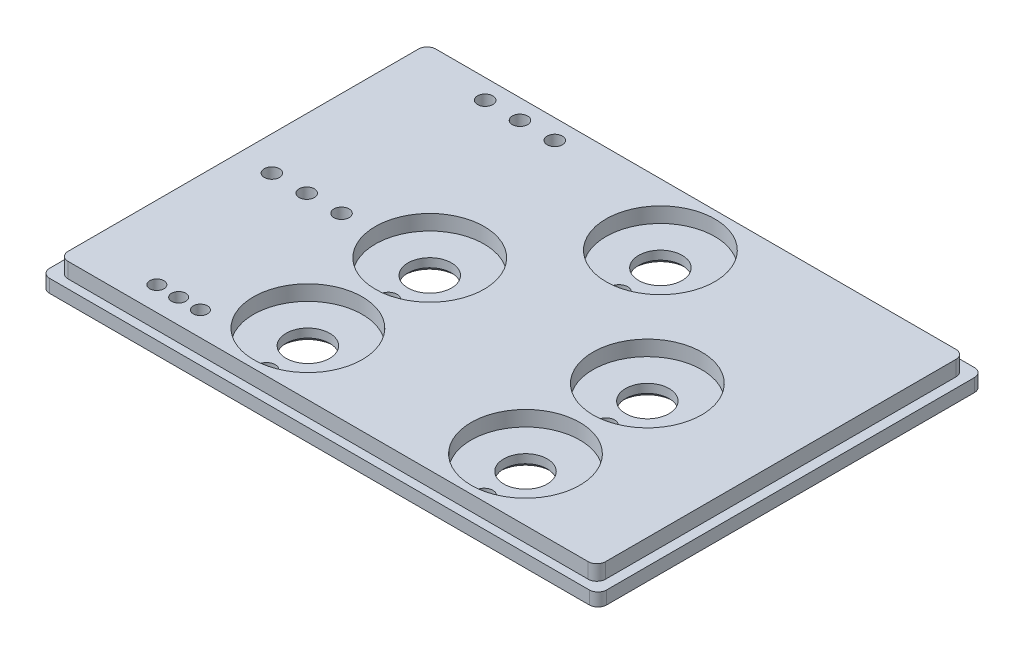
SolidWorks part; units mm, degrees
ref_plane "Спереди" through (0, 0, 0) normal (0, 0, 1) x (1, 0, 0)
ref_plane "Сверху" through (0, 0, 0) normal (0, 1, 0) x (1, 0, 0)
ref_plane "Справа" through (0, 0, 0) normal (1, 0, 0) x (0, 0, -1)
sketch "Эскиз1" plane through (0, 37.5, 0) normal (0, 1, 0) x (1, 0, 0)
  line L1 (127, -2) -> (127, 87) construction
  line L2 (-2, 87) -> (0, 87) construction
  line L3 (127, -2) -> (127, 87) construction
  line L4 (127, -2) -> (0, -2) construction
  line L5 (127, -2) -> (-2, -2) construction
  line L6 (-2, 87) -> (-2, -2) construction
  line L7 (-2, 87) -> (-2, -2) construction
  line L8 (62.5, 87) -> (62.5, -2) construction
  line L9 (-2, 87) -> (0, 87) construction
  line L10 (-2, 86.75) -> (127, 86.75)
  line L11 (-2, 86.75) -> (-2, -1.75)
  line L12 (-2, -1.75) -> (127, -1.75)
  line L13 (127, 86.75) -> (127, -1.75)
  line L14 (-2, 86.75) -> (127, -1.75) construction
  line L15 (-2, -1.75) -> (127, 86.75) construction
  point P8 (62.5, 42.5)
  dimension "D1" = 0.25
  dimension "D2" = 0.25
extrude "Бобышка-Вытянуть1" add sketch "Эскиз1" along normal blind 3
sketch "Эскиз2" plane through (0, 40.5, 0) normal (0, 1, 0) x (1, 0, 0)
  circle A0 centre (43.6, 14.5) radius 5 construction
  circle A1 centre (43.6, 14.5) radius 5 construction
  circle A3 centre (43.6, 42.5) radius 5 construction
  circle A4 centre (68.6, 70.5) radius 5 construction
  circle A5 centre (68.6, 70.5) radius 5 construction
  circle A6 centre (43.6, 42.5) radius 5 construction
  circle A7 centre (93.6, 42.5) radius 5 construction
  circle A8 centre (93.6, 42.5) radius 5 construction
  circle A9 centre (93.6, 14.5) radius 5 construction
  circle A10 centre (93.6, 14.5) radius 5 construction
  circle A11 centre (43.6, 14.5) radius 5
  circle A12 centre (43.6, 42.5) radius 5
  circle A13 centre (68.6, 70.5) radius 5
  circle A14 centre (93.6, 42.5) radius 5
  circle A15 centre (93.6, 14.5) radius 5
  dimension "D1" = 0
extrude "Вырез-Вытянуть1" cut sketch "Эскиз2" against normal through all
sketch "Эскиз3" plane through (0, 40.5, 0) normal (0, 1, 0) x (1, 0, 0)
  circle A0 centre (34.5998, 80.2301) radius 1.75
  circle A1 centre (27.5999, 5.8) radius 1.5
  circle A2 centre (27.5999, 5.8) radius 1.5 construction
  circle A3 centre (22.5999, 5.8) radius 1.5
  circle A4 centre (22.5999, 5.8) radius 1.5 construction
  circle A5 centre (17.5999, 5.8) radius 1.5
  circle A6 centre (17.5999, 5.8) radius 1.5 construction
  circle A7 centre (34.5998, 80.2301) radius 1.5
  circle A8 centre (34.5998, 80.2301) radius 1.5 construction
  circle A9 centre (26.6, 80.2299) radius 1.5
  circle A10 centre (26.6, 80.2299) radius 1.5 construction
  circle A11 centre (18.5998, 80.2301) radius 1.5
  circle A12 centre (18.5998, 80.2301) radius 1.5 construction
  circle A13 centre (8.5998, 41.2301) radius 1.5
  circle A14 centre (8.5998, 41.2301) radius 1.5 construction
  circle A15 centre (16.5998, 41.2301) radius 1.5
  circle A16 centre (16.5998, 41.2301) radius 1.5 construction
  circle A17 centre (24.6, 41.2299) radius 1.5
  circle A18 centre (24.6, 41.2299) radius 1.5 construction
  circle A19 centre (26.6, 80.2299) radius 1.75
  circle A20 centre (18.5998, 80.2301) radius 1.75
  circle A21 centre (8.5998, 41.2301) radius 1.75
  circle A22 centre (16.5998, 41.2301) radius 1.75
  circle A23 centre (24.6, 41.2299) radius 1.75
  circle A24 centre (27.5999, 5.8) radius 1.625
  circle A25 centre (22.5999, 5.8) radius 1.625
  circle A26 centre (17.5999, 5.8) radius 1.625
  dimension "D10" = 3.5
  dimension "D11" = 3.25
  dimension "D1" = 0
  dimension "D2" = 0
  dimension "D3" = 0
  dimension "D4" = 0
  dimension "D5" = 0
  dimension "D6" = 0
  dimension "D7" = 0
  dimension "D8" = 0
  dimension "D9" = 0
extrude "Вырез-Вытянуть2" cut sketch "Эскиз3" against normal through all
chamfer "Фаска1" distance 1 angle 45 5 edges at (93.6, 37.5, -9.5) (93.6, 37.5, -37.5) (68.6, 37.5, -65.5) (43.6, 37.5, -37.5) (43.6, 37.5, -9.5)
sketch "Эскиз6" plane through (0, 40.5, 0) normal (0, 1, 0) x (1, 0, 0)
  line L0 (125, 0) -> (0, 0) construction
  line L1 (125, 0) -> (125, 85) construction
  line L2 (125, 0) -> (0, 0) construction
  line L3 (125, 0) -> (125, 85) construction
  line L4 (0, -4) -> (0, 89) construction
  line L5 (0, -4) -> (0, 89) construction
  line L6 (125, 85) -> (0, 85) construction
  line L7 (125, 85) -> (0, 85) construction
  line L8 (62.5, 85) -> (62.5, 0) construction
  line L10 (124.75, 0.25) -> (0.25, 0.25)
  line L11 (124.75, 0.25) -> (124.75, 84.75)
  line L12 (124.75, 84.75) -> (0.25, 84.75)
  line L13 (0.25, 0.25) -> (0.25, 84.75)
  line L14 (124.75, 0.25) -> (0.25, 84.75) construction
  line L15 (124.75, 84.75) -> (0.25, 0.25) construction
  point P8 (62.5, 42.5)
  dimension "D1" = 0.25
  dimension "D2" = 0.25
extrude "Бобышка-Вытянуть3" add sketch "Эскиз6" along normal blind 3.5
sketch "Эскиз7" plane through (0, 40.5, 0) normal (0, -1, 0) x (1, 0, 0)
  circle A0 centre (26.6, -80.2299) radius 1.75 construction
  circle A1 centre (43.6, -42.5) radius 5
  circle A2 centre (43.6, -42.5) radius 5
  circle A3 centre (43.6, -14.5) radius 5
  circle A4 centre (43.6, -14.5) radius 5
  circle A5 centre (93.6, -14.5) radius 5
  circle A6 centre (93.6, -14.5) radius 5
  circle A7 centre (93.6, -42.5) radius 5
  circle A8 centre (93.6, -42.5) radius 5
  circle A9 centre (68.6, -70.5) radius 5
  circle A10 centre (68.6, -70.5) radius 5
  circle A11 centre (24.6, -41.2299) radius 1.75
  circle A12 centre (24.6, -41.2299) radius 1.75
  circle A13 centre (16.5998, -41.2301) radius 1.75
  circle A14 centre (16.5998, -41.2301) radius 1.75
  circle A15 centre (8.5998, -41.2301) radius 1.75
  circle A16 centre (8.5998, -41.2301) radius 1.75
  circle A17 centre (18.5998, -80.2301) radius 1.75
  circle A18 centre (18.5998, -80.2301) radius 1.75
  circle A19 centre (26.6, -80.2299) radius 1.75
  circle A21 centre (34.5998, -80.2301) radius 1.75
  circle A22 centre (34.5998, -80.2301) radius 1.75
  circle A25 centre (22.5999, -5.8) radius 1.625 construction
  circle A26 centre (22.5999, -5.8) radius 1.625
  circle A27 centre (17.5999, -5.8) radius 1.625 construction
  circle A28 centre (27.5999, -5.8) radius 1.625 construction
  circle A29 centre (27.5999, -5.8) radius 1.625
  circle A30 centre (17.5999, -5.8) radius 1.625
  dimension "D1" = 0
  dimension "D2" = 0
  dimension "D3" = 0
  dimension "D4" = 0
  dimension "D5" = 0
  dimension "D6" = 0
  dimension "D7" = 0
  dimension "D8" = 0
  dimension "D9" = 0
  dimension "D10" = 0
extrude "Вырез-Вытянуть3" cut sketch "Эскиз7" against normal through all
sketch "Эскиз9" plane through (0, 44, 0) normal (0, 1, 0) x (1, 0, 0)
  circle A0 centre (43.6, 14.5) radius 12.5
  circle A1 centre (43.6, 42.5) radius 12.5
  circle A2 centre (68.6, 70.5) radius 12.5
  circle A3 centre (93.6, 42.5) radius 12.5
  circle A4 centre (93.6, 14.5) radius 12.5
  dimension "D1" = 25
extrude "Вырез-Вытянуть4" cut sketch "Эскиз9" against normal blind 3.5
sketch "Эскиз10" plane through (0, 44, 0) normal (0, 1, 0) x (1, 0, 0)
  circle A0 centre (93.6, 33) radius 1.5 construction
  circle A1 centre (93.6, 33) radius 1.5 construction
  circle A2 centre (93.6, 5) radius 1.5 construction
  circle A3 centre (93.6, 5) radius 1.5 construction
  circle A4 centre (43.6, 5) radius 1.5 construction
  circle A5 centre (43.6, 5) radius 1.5 construction
  circle A6 centre (43.6, 33) radius 1.5 construction
  circle A7 centre (43.6, 33) radius 1.5 construction
  circle A8 centre (68.6, 61.0001) radius 1.5 construction
  circle A9 centre (68.6, 61.0001) radius 1.5 construction
  circle A10 centre (43.6, 5) radius 2
  circle A11 centre (43.6, 33) radius 2
  circle A12 centre (68.6, 61.0001) radius 2
  circle A13 centre (93.6, 33) radius 2
  circle A14 centre (93.6, 5) radius 2
  dimension "D1" = 0.5
sketch "Эскиз11" plane through (0, 37.5, 0) normal (0, -1, 0) x (1, 0, 0)
  circle A0 centre (43.6, -5) radius 2 construction
  circle A1 centre (43.6, -33) radius 2 construction
  circle A2 centre (93.6, -5) radius 2 construction
  circle A3 centre (93.6, -33) radius 2 construction
  circle A4 centre (68.6, -61.0001) radius 2 construction
  circle A5 centre (43.6, -5) radius 2
  circle A6 centre (43.6, -33) radius 2
  circle A7 centre (93.6, -5) radius 2
  circle A8 centre (93.6, -33) radius 2
  circle A9 centre (68.6, -61.0001) radius 2
extrude "Вырез-Вытянуть5" cut sketch "Эскиз11" against normal up to surface (3 mm away) up to face at (93.6, 40.5, -2)
sketch "Sketch1" plane through (-2, 0, 0) normal (-1, 0, 0) x (0, 0, 1)
  line L4 (-86.75, 37.5) -> (1.75, 37.5)
  line L5 (1.75, 37.5) -> (1.75, 40.5)
  line L6 (1.75, 40.5) -> (-86.75, 40.5)
  line L7 (-86.75, 40.5) -> (-86.75, 37.5)
  line L8 (-86.75, 37.5) -> (1.75, 37.5)
  line L9 (1.75, 37.5) -> (1.75, 40.5)
  line L10 (1.75, 40.5) -> (-86.75, 40.5)
  line L11 (-86.75, 40.5) -> (-86.75, 37.5)
  dimension "D1" = 0
extrude "Cut-Extrude1" cut sketch "Sketch1" against normal blind 0.5
sketch "Sketch2" plane through (127, 0, 0) normal (1, 0, 0) x (0, 0, -1)
  line L4 (-1.75, 37.5) -> (86.75, 37.5)
  line L5 (86.75, 37.5) -> (86.75, 40.5)
  line L6 (86.75, 40.5) -> (-1.75, 40.5)
  line L7 (-1.75, 40.5) -> (-1.75, 37.5)
  line L8 (-1.75, 37.5) -> (86.75, 37.5)
  line L9 (86.75, 37.5) -> (86.75, 40.5)
  line L10 (86.75, 40.5) -> (-1.75, 40.5)
  line L11 (-1.75, 40.5) -> (-1.75, 37.5)
  dimension "D1" = 0
extrude "Cut-Extrude2" cut sketch "Sketch2" against normal blind 0.5
sketch "Sketch3" plane through (124.75, 0, 0) normal (1, 0, 0) x (0, 0, -1)
  line L4 (0.25, 40.5) -> (84.75, 40.5)
  line L5 (84.75, 40.5) -> (84.75, 44)
  line L6 (84.75, 44) -> (0.25, 44)
  line L7 (0.25, 44) -> (0.25, 40.5)
  line L8 (0.25, 40.5) -> (84.75, 40.5)
  line L9 (84.75, 40.5) -> (84.75, 44)
  line L10 (84.75, 44) -> (0.25, 44)
  line L11 (0.25, 44) -> (0.25, 40.5)
  dimension "D1" = 0
extrude "Cut-Extrude3" cut sketch "Sketch3" against normal blind 0.5
sketch "Sketch4" plane through (0.25, 0, 0) normal (-1, 0, 0) x (0, 0, 1)
  line L4 (-84.75, 40.5) -> (-0.25, 40.5)
  line L5 (-0.25, 40.5) -> (-0.25, 44)
  line L6 (-0.25, 44) -> (-84.75, 44)
  line L7 (-84.75, 44) -> (-84.75, 40.5)
  line L8 (-84.75, 40.5) -> (-0.25, 40.5)
  line L9 (-0.25, 40.5) -> (-0.25, 44)
  line L10 (-0.25, 44) -> (-84.75, 44)
  line L11 (-84.75, 44) -> (-84.75, 40.5)
  dimension "D1" = 0
extrude "Cut-Extrude4" cut sketch "Sketch4" against normal blind 0.5
fillet "Fillet1" radius 2 8 edges at (126.5, 39, -86.75) (124.25, 42.25, -84.75) (126.5, 39, 1.75) (124.25, 42.25, -0.25) (0.75, 42.25, -0.25) (-1.5, 39, 1.75) (0.75, 42.25, -84.75) (-1.5, 39, -86.75)
sketch "Sketch5" plane through (0, 37.5, 0) normal (0, -1, 0) x (1, 0, 0)
  circle A0 centre (8.5998, -41.2301) radius 1.75 construction
  circle A1 centre (16.5998, -41.2301) radius 1.75 construction
  circle A2 centre (24.6, -41.2299) radius 1.75 construction
  circle A3 centre (18.5998, -80.2301) radius 1.75 construction
  circle A4 centre (26.6, -80.2299) radius 1.75 construction
  circle A5 centre (34.5998, -80.2301) radius 1.75 construction
  circle A6 centre (8.5998, -41.2301) radius 1.75 construction
  circle A7 centre (16.5998, -41.2301) radius 1.75 construction
  circle A8 centre (24.6, -41.2299) radius 1.75 construction
  circle A9 centre (18.5998, -80.2301) radius 1.75 construction
  circle A10 centre (26.6, -80.2299) radius 1.75 construction
  circle A11 centre (34.5998, -80.2301) radius 1.75 construction
  circle A12 centre (8.5998, -41.2301) radius 2.5
  circle A13 centre (16.5998, -41.2301) radius 2.5
  circle A14 centre (24.6, -41.2299) radius 2.5
  circle A15 centre (18.5998, -80.2301) radius 2.5
  circle A16 centre (26.6, -80.2299) radius 2.5
  circle A17 centre (34.5998, -80.2301) radius 2.5
  dimension "D1" = 5
extrude "Cut-Extrude5" cut sketch "Sketch5" against normal blind 2
chamfer "Chamfer1" distance 1 angle 45 6 edges at (34.5998, 37.5, -82.7301) (26.6, 37.5, -82.7299) (18.5998, 37.5, -82.7301) (24.6, 37.5, -43.7299) (16.5998, 37.5, -43.7301) (8.5998, 37.5, -43.7301)
